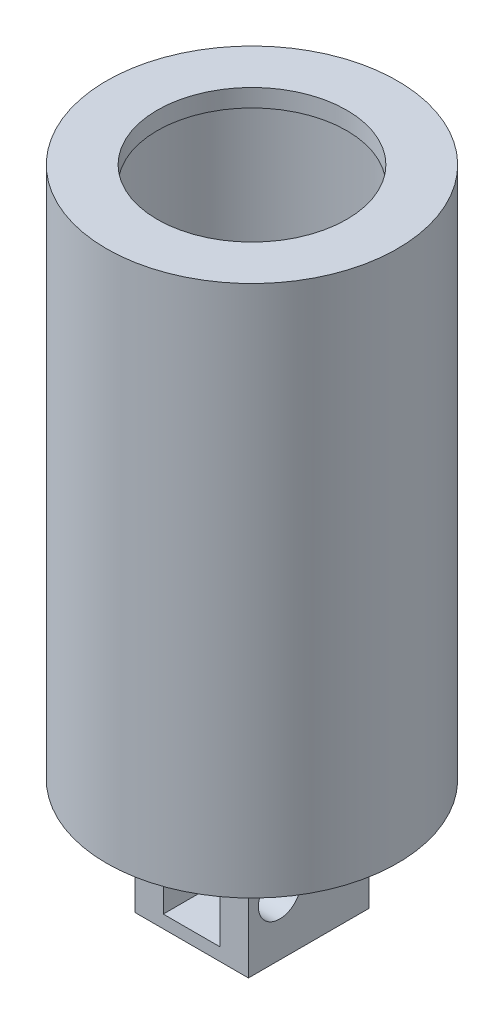
SolidWorks part; units mm, degrees
note: The reader was unsure of these and kept them because the rebuilt part matched: shared geometry of "Sketch4<3>".
material "ABS"
ref_plane "Front Plane" through (0, 0, 0) normal (0, 0, 1) x (1, 0, 0)
ref_plane "Top Plane" through (0, 0, 0) normal (0, 1, 0) x (1, 0, 0)
ref_plane "Right Plane" through (0, 0, 0) normal (1, 0, 0) x (0, 0, -1)
sketch "Sketch1" plane through (0, 0, 0) normal (0, 0, 1) x (1, 0, 0)
  line L0 (0, 9.278) -> (0, 1.278) construction
  line L1 (-6.6742, -1.25) -> (-6.6742, 0)
  line L2 (-6.6742, 0) -> (-10.25, 0)
  line L3 (-10.25, 0) -> (-10.25, -36.5)
  line L4 (-6.6742, -1.25) -> (-9, -1.25)
  line L5 (-9, -1.25) -> (-9, -36.5)
  line L6 (-9, -36.5) -> (-10.25, -36.5)
  line L12 (0, -40.3709) -> (0, 7.6905) construction
  dimension "D1" = 1.25
  dimension "D2" = 9
  dimension "D3" = 1.25
  dimension "D4" = 36.5
  dimension "D5" = 3.5758
revolve "Revolve1" add sketch "Sketch1" angle 360 about L0
sketch "Sketch2" plane through (0, -36.5, 0) normal (0, -1, 0) x (1, 0, 0)
  circle A0 centre (0, 0) radius 10.25
  circle A1 centre (0, 0) radius 10.25 construction
extrude "Boss-Extrude1" add sketch "Sketch2" along normal blind 1
sketch "Sketch3" plane through (0, -37.5, 0) normal (0, -1, 0) x (1, 0, 0)
  line L0 (-4, 4.25) -> (4, 4.25)
  line L1 (-4, -4.25) -> (4, -4.25)
  line L2 (0, 10.25) -> (0, -10.25) construction
  line L5 (4, 4.25) -> (4, -4.25)
  line L7 (-4, -4.25) -> (-4, 4.25)
  circle A0 centre (0, 0) radius 10.25 construction
  circle A1 centre (0, 0) radius 10.25 construction
  point P8 (0, 4.25)
  dimension "D1" = 4.25
  dimension "D2" = 4
  dimension "D3" = 4.25
extrude "Boss-Extrude2" add sketch "Sketch3" along normal blind 8
sketch "Sketch4" plane through (4, 0, -0.2768) normal (-1, 0, 0) x (0, 0, 1)
  line L0 (4.5268, -44.6) -> (4.5268, -38.4)
  line L1 (4.5268, -45.5) -> (4.5268, -37.5) construction
  line L2 (4.5268, -38.4) -> (-0.4732, -38.4)
  line L3 (4.5268, -44.6) -> (-0.4732, -44.6)
  line L4 (4.5268, -41.5) -> (-3.9732, -41.5) construction
  line L7 (-3.9732, -45.5) -> (-3.9732, -37.5) construction
  arc A0 (-0.4732, -38.4) -> (-0.4732, -44.6) centre (-0.4732, -41.5) ccw
  circle A1 centre (2.3268, -41.5) radius 1.5
  point P6 (4.5268, -41.5)
  line M15 (4.5268, -37.5) -> (4.5268, -45.5)
  dimension "D1" = 6.2
  dimension "D2" = 2.2
  dimension "D5" = 5
extrude "Cut-Extrude1" cut sketch "Sketch4" against normal mid plane 4 from offset 4 contours L4 A1 A0 L2 M15 | L4 L0 L3 A0 A1
extrude "Cut-Extrude3" cut sketch "Sketch4<3>" along normal up to surface (8 mm away) contours A1 L4 | L4 A1 up to face at (-4, -41.5, 0)
sketch "Sketch4<3>" plane through (4, 0, -0.2768) normal (-1, 0, 0) x (0, 0, 1) same geometry as "Sketch4"
